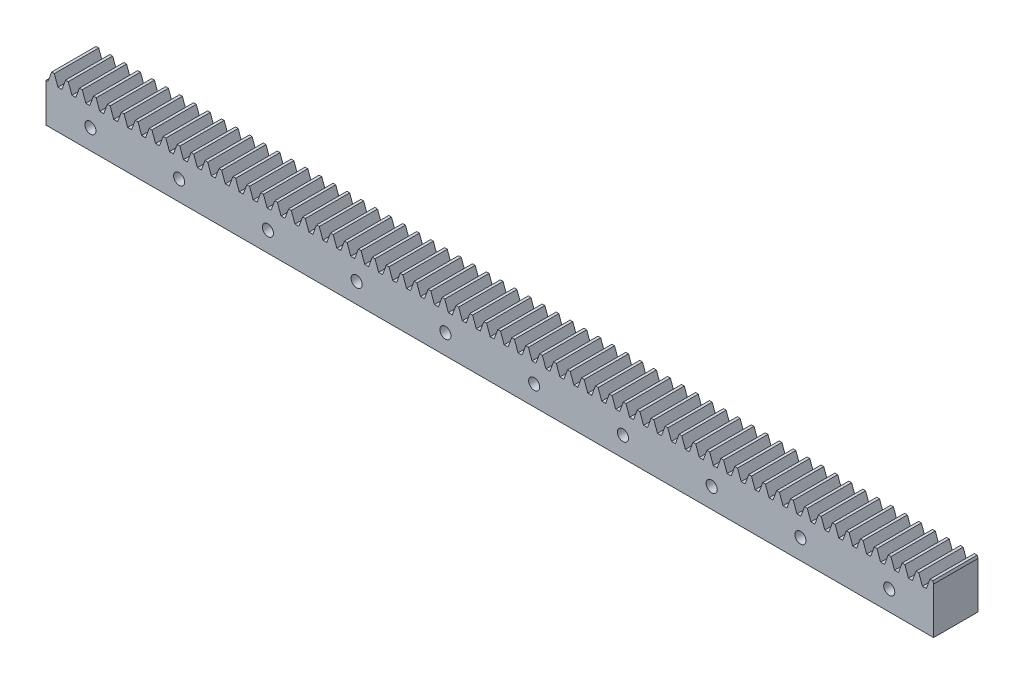
SolidWorks part; units mm, degrees
extrude "Blank" add sketch "BlankSke" against normal blind 10
sketch "BlankSke" plane through (0, 0, 0) normal (0, 0, 1) x (1, 0, 0)
  line L1 (0, 0) -> (200, 0)
  line L2 (0, 0) -> (0, 11)
  line L3 (0, 11) -> (200, 11)
  line L4 (200, 0) -> (200, 11)
  dimension "Length" = 200
material "鑄碳鋼"
ref_plane "Plane1" through (0, 0, 0) normal (0, 0, 1) x (1, 0, 0)
ref_plane "Plane2" through (0, 0, 0) normal (0, 1, 0) x (1, 0, 0)
ref_plane "Plane3" through (0, 0, 0) normal (1, 0, 0) x (0, 0, -1)
sketch "HoldingSke" plane through (0, 0, 0) normal (0, 1, 0) x (1, 0, 0)
  line L0 (0, 0) -> (-0.766, -0.6428)
  line L1 (-15, 0) -> (100, 0) construction
  line L2 (0, 0) -> (-2.1039, 2.3779)
  line L3 (0, 0) -> (-11.863, 4.5341)
  line L4 (0, 0) -> (-1.0524, 8.5716)
  line L5 (0, 0) -> (-23.7986, -8.8762)
  line L6 (0, 0) -> (-10.5278, -7.1032)
  line L9 (-71.009, 38.7566) -> (210.8988, 141.3627)
  line L10 (-76.2, 3.3779) -> (-66.2, 3.3779)
  line L11 (0, 0) -> (-6.35, 0)
  line L12 (-76.2, 101.6) -> (-76.162, 101.6)
  line L13 (24.9733, 27.94) -> (52.9518, 28.4284)
  line L14 (24.9733, 27.94) -> (24.9743, 27.94)
  line L15 (24.9733, 27.94) -> (100.4006, 29.5858)
  circle A0 centre (0, 0) radius 19.05
  circle A1 centre (0, 0) radius 5
  circle A2 centre (0, 0) radius 12.7
  dimension "Num_teeth" = 97
  dimension "Width" = 6.35
  dimension "Pitch_height" = 10
sketch "TooCutSkeIll" plane through (0, 0, 0) normal (0, 0, 1) x (1, 0, 0)
  line L0 (-1.2538, 10.9737) -> (-0.5045, 8.9152)
  line L1 (-0.2687, 8.75) -> (0.2687, 8.75)
  line L2 (0.5045, 8.9152) -> (1.2538, 10.9737)
  line L3 (200, 11) -> (0, 11) construction
  line L4 (0, 0) -> (0, 64.897) construction
  line L5 (-13.208, 10) -> (12.954, 10) construction
  line L6 (0, 0) -> (200, 0) construction
  line L7 (0.8994, 10) -> (0.8994, 48.7463) construction
  line L8 (-0.8994, 10) -> (-0.8994, 48.7463) construction
  line L9 (1.2914, 11) -> (1.2914, 11.0254)
  line L10 (-1.2914, 11) -> (-1.2914, 11.0254)
  line L11 (-1.2914, 11.0254) -> (1.2914, 11.0254)
  arc A0 (0.2687, 8.75) -> (0.5045, 8.9152) centre (0.2687, 9.001) ccw
  arc A1 (-0.5045, 8.9152) -> (-0.2687, 8.75) centre (-0.2687, 9.001) ccw
  arc A2 (1.2914, 11) -> (1.2538, 10.9737) centre (1.2914, 10.96) ccw
  arc A3 (-1.2538, 10.9737) -> (-1.2914, 11) centre (-1.2914, 10.96) ccw
  dimension "Addendum_plus" = 1.0254
  dimension "Pitch_height" = 10
  dimension "Pressure_angle" = 20
  dimension "Gap_width" = 1.7988
  dimension "Dedendum" = 1.25
extrude "ToothCutIll" [suppressed] cut sketch "TooCutSkeIll" against normal through all
sketch "TooCutSkeSim" plane through (0, 0, 0) normal (0, 0, 1) x (1, 0, 0)
  line L0 (0.4444, 8.75) -> (-0.4444, 8.75)
  line L1 (1.2726, 11.0254) -> (0.4444, 8.75)
  line L2 (0, 17.4625) -> (0, 53.467) construction
  line L3 (1.2726, 11.0254) -> (-1.2726, 11.0254)
  line L6 (-1.2726, 11.0254) -> (-0.4444, 8.75)
  line L9 (-0.8994, 10) -> (0.8994, 10) construction
  line L10 (0, 0) -> (200, 0) construction
  line L11 (0.8994, 10) -> (0.8994, 53.467) construction
  line L12 (-0.8994, 10) -> (-0.8994, 53.467) construction
  dimension "Addendum_plus" = 1.0254
  dimension "Pitch_height" = 10
  dimension "Pressure_angle" = 20
  dimension "Gap_width" = 1.7988
  dimension "Dedendum" = 1.25
extrude "ToothCutSim" cut sketch "TooCutSkeSim" against normal through all
pattern_linear "TeethCuts" count 97 spacing 3.1416 along (1, 0, 0) of "ToothCutIll", "ToothCutSim"
hole_wizard "M3x0.5 螺紋孔1" positions "3D草圖1" profile "草圖2" tap size "M3x0.5" standard "Ansi Metric" end condition through all
sketch3d "3D草圖1"
  line L0 (0, 0, 0) -> (200, 0, 0) construction
  line L1 (0, 8.75, 0) -> (0, 0, 0) construction
  point P0 (10, 4.5, 0)
  dimension "D1" = 4.5
  dimension "D2" = 10
sketch "草圖2" plane through (10, 4.5, 0) normal (1, 0, 0) x (0, -1, 0)
  line L0 (0, 0) -> (0, 10)
  line L1 (0, 10) -> (1.25, 10)
  line L2 (1.25, 10) -> (1.25, 0)
  line L5 (1.25, 0) -> (0, 0)
  line L11 (0, -6.35) -> (0, 107.95) construction
  dimension "貫穿螺孔鑽直徑" = 2.5
  dimension "貫穿螺孔鑽深度" = 10
pattern_linear "直線複製排列1" count 15 spacing 20 along (1, 0, 0) of "M3x0.5 螺紋孔1"
equation "' \"Module@HoldingSke\" = 6.35"
equation "' \"Num_teeth@HoldingSke\" = 12"
equation "' \"Ap@HoldingSke\" =  20"
equation "' \"Ap@HoldingSke\" = 20"
equation "' \"Width@HoldingSke\" = 0.25 * 25.4"
equation "' \"Show_teeth@HoldingSke\" = 500"
equation "' \"Backlash@HoldingSke\" = 0.009 * 25.4"
equation "' \"Addendum_fac@HoldingSke\" = 1.0"
equation "' \"Dedendum_fac@HoldingSke\" = 1.25"
equation "' \"Dedendum_add@HoldingSke\" = 0.00005 * 25.4"
equation "' \"Clearance_fac@HoldingSke\" = 0.25"
equation "' \"Pitch_height@HoldingSke\" = 1 * 25.4"
equation "' \"Length@HoldingSke\" = 4.71 * 25.4"
equation "\"Pitch@HoldingSke\" = 1 / \"Module@HoldingSke\""
equation "\"MPH@HoldingSke\" = \"Dedendum_fac@HoldingSke\" / \"Pitch@HoldingSke\" + 2 * \"Dedendum_add@HoldingSke\" + 0.002 * 25.4"
equation "\"MPH@HoldingSke\" = ((sgn( \"MPH@HoldingSke\" - \"Pitch_height@HoldingSke\")+1)*( \"MPH@HoldingSke\" - \"Pitch_height@HoldingSke\"))/2 + \"Pitch_height@HoldingSke\""
equation "\"Blank_height@BlankSke\" = \"Pitch_height@HoldingSke\" + \"Addendum_fac@HoldingSke\"  / \"Pitch@HoldingSke\" "
equation "\"Pressure_angle@TooCutSkeIll\" = \"Ap@HoldingSke\""
equation "\"Addendum_plus@TooCutSkeIll\" =  \"Addendum_fac@HoldingSke\"  / \"Pitch@HoldingSke\" + 0.001 *25.4"
equation "\"Dedendum@TooCutSkeIll\" = \"Dedendum_fac@HoldingSke\"  / \"Pitch@HoldingSke\""
equation "\"Pitch_height@TooCutSkeIll\" =  \"MPH@HoldingSke\""
equation "\"Gap_width@TooCutSkeIll\" = 3.14159265 / 2 / \"Pitch@HoldingSke\" + 6 * \"Backlash@HoldingSke\""
equation "\"Pressure_angle@TooCutSkeSim\" = \"Ap@HoldingSke\""
equation "\"Addendum_plus@TooCutSkeSim\" =  \"Addendum_fac@HoldingSke\"  / \"Pitch@HoldingSke\" + 0.001 * 25.4"
equation "\"Dedendum@TooCutSkeSim\" = \"Dedendum_fac@HoldingSke\"  / \"Pitch@HoldingSke\""
equation "\"Pitch_height@TooCutSkeSim\" =  \"MPH@HoldingSke\""
equation "\"Gap_width@TooCutSkeSim\" = 3.14159265 / 2 / \"Pitch@HoldingSke\" + 6 * \"Backlash@HoldingSke\""
equation "\"Root_fillet@TooCutSkeIll\" = \"Clearance_fac@HoldingSke\" / \"Pitch@HoldingSke\" + \"Dedendum_add@HoldingSke\""
equation "\"Break_rad@TooCutSkeIll\" = 0.02 / \"Pitch@HoldingSke\" * 2"
equation "\"Linear_pitch@TeethCuts\" = 3.14159265 / \"Pitch@HoldingSke\""
equation "\"Num_teeth@HoldingSke\" = int( ( \"Length@HoldingSke\" + 0 ) / (3.14159265 / \"Pitch@HoldingSke\")) + 0.9999  + 1"
equation " \"Num_teeth@TeethCuts\" = int( \"Show_teeth@HoldingSke\" ) + 1"
equation " \"Num_teeth@TeethCuts\" = ((sgn( \"Num_teeth@TeethCuts\" - \"Num_teeth@HoldingSke\" )-1)*( \"Num_teeth@TeethCuts\" - \"Num_teeth@HoldingSke\" ))/-2+ \"Num_teeth@HoldingSke\""
equation " \"Num_teeth@TeethCuts\" = ((sgn( \"Num_teeth@TeethCuts\" - 2.0)+1)*( \"Num_teeth@TeethCuts\" - 2.0))/2 +2.0"
